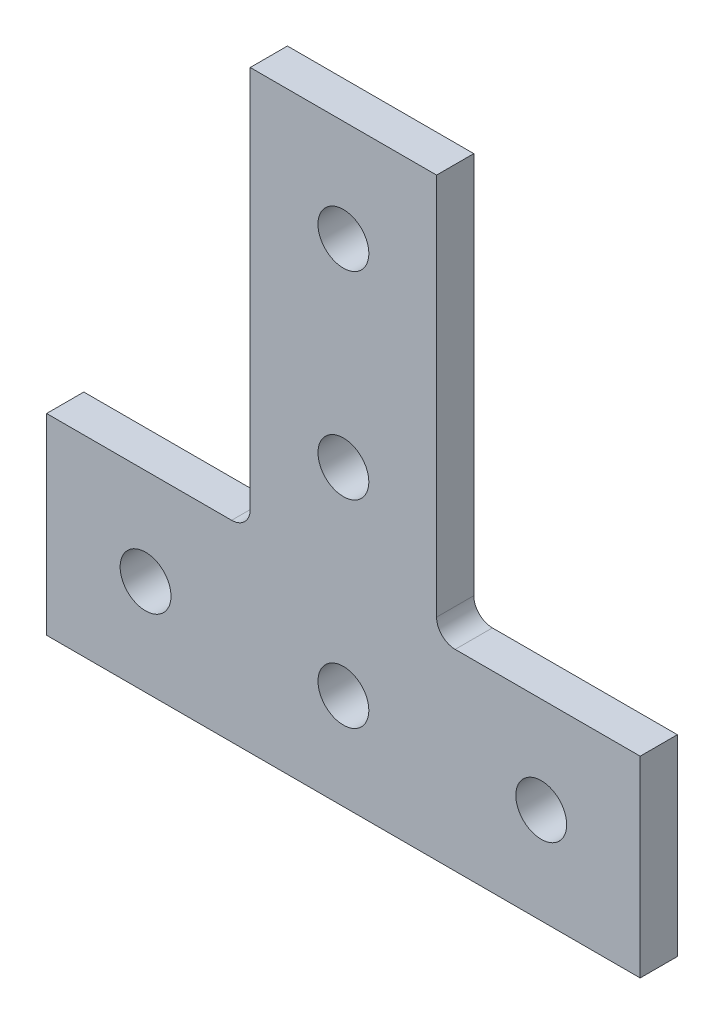
SolidWorks part; units mm, degrees
material "6061 Alloy"
ref_plane "Front Plane" through (0, 0, 0) normal (0, 0, 1) x (1, 0, 0)
ref_plane "Top Plane" through (0, 0, 0) normal (0, 1, 0) x (1, 0, 0)
ref_plane "Right Plane" through (0, 0, 0) normal (1, 0, 0) x (0, 0, -1)
sketch "Sketch1" plane through (0, 0, 0) normal (0, 0, 1) x (1, 0, 0)
  line L0 (0, 38.1) -> (0, -38.1) construction
  line L1 (-38.1, -38.1) -> (38.1, -38.1) construction
  line L2 (38.1, -38.1) -> (38.1, -13.4366) construction
  line L3 (25.4, -22.5044) -> (25.4, -29.0322) construction
  line L4 (11.9634, 38.1) -> (-11.9634, 38.1) construction
  point P0 (0, -0.3683)
  point P4 (0, 0)
  point P8 (0, -38.1)
  point P11 (25.4, -25.7683)
  point P12 (38.1, -25.7683)
  point P15 (0, 38.1)
  dimension "Length" = 76.2
  dimension "Width1" = 24.6634
  dimension "Hole Dia" = 6.5278
  dimension "Hole to Edge" = 12.7
  dimension "Hole Spacing" = 25.4
  dimension "Width2" = 23.9268
sketch "Sketch2" plane through (0, 0, 0) normal (1, 0, 0) x (0, 0, -1)
  line L0 (2.3876, 0) -> (-2.3876, 0) construction
  point P4 (0, 0)
  dimension "Thickness" = 4.7752
sketch "Sketch3" plane through (0, 0, 0) normal (0, 0, 1) x (1, 0, 0)
  line L0 (38.1, -38.1) -> (-38.1, -38.1)
  line L1 (38.1, -38.1) -> (38.1, -13.4366)
  line L2 (38.1, -13.4366) -> (14.351, -13.4366)
  line L3 (11.9634, -11.049) -> (11.9634, 38.1)
  line L4 (11.9634, 38.1) -> (-11.9634, 38.1)
  line L5 (11.9634, 38.1) -> (-11.9634, 38.1) construction
  line L6 (-38.1, -38.1) -> (38.1, -38.1) construction
  line L7 (0, -38.1) -> (0, 38.1) construction
  line L8 (-11.9634, -11.049) -> (-11.9634, 38.1)
  line L9 (-38.1, -13.4366) -> (-14.351, -13.4366)
  line L10 (-38.1, -38.1) -> (-38.1, -13.4366)
  arc A0 (-11.9634, -11.049) -> (-14.351, -13.4366) centre (-14.351, -11.049) cw
  arc A1 (14.351, -13.4366) -> (11.9634, -11.049) centre (14.351, -11.049) cw
  point P20 (-11.9634, -13.4366)
  point P23 (11.9634, -13.4366)
  dimension "Radius" = 2.3876
extrude "Boss-Extrude1" add sketch "Sketch3" against normal up to vertex (2.3876 mm away) and the other way up to vertex (2.3876 mm away) up to point (0, 0, -2.3876) other way up to point (0, 0, 2.3876)
sketch "Sketch4" plane through (0, 0, 2.3876) normal (0, 0, 1) x (1, 0, 0)
  line L0 (25.4, -22.5044) -> (25.4, -29.0322) construction
  line L1 (0, 38.1) -> (0, -38.1) construction
  line L2 (0, -38.1) -> (0, 38.1) construction
  line L3 (-38.1, -38.1) -> (38.1, -38.1) construction
  line L4 (0, -0.3683) -> (-11.9634, -0.3683) construction
  line L5 (-11.9634, 38.1) -> (-11.9634, -11.049) construction
  circle A0 centre (25.4, -25.7683) radius 3.2639
  circle A1 centre (0, -25.7683) radius 3.2639
  circle A2 centre (-25.4, -25.7683) radius 3.2639
  circle A3 centre (0, -0.3683) radius 3.2639
  circle A4 centre (0, 25.0317) radius 3.2639
extrude "Cut-Extrude1" cut sketch "Sketch4" against normal through all
ref_plane "Plane1" through (0, 0, 0) normal (-1, 0, 0) x (0, 0, 1)
ref_plane "Plane2" through (0, -25.7683, 0) normal (0, 1, 0) x (1, 0, 0)
